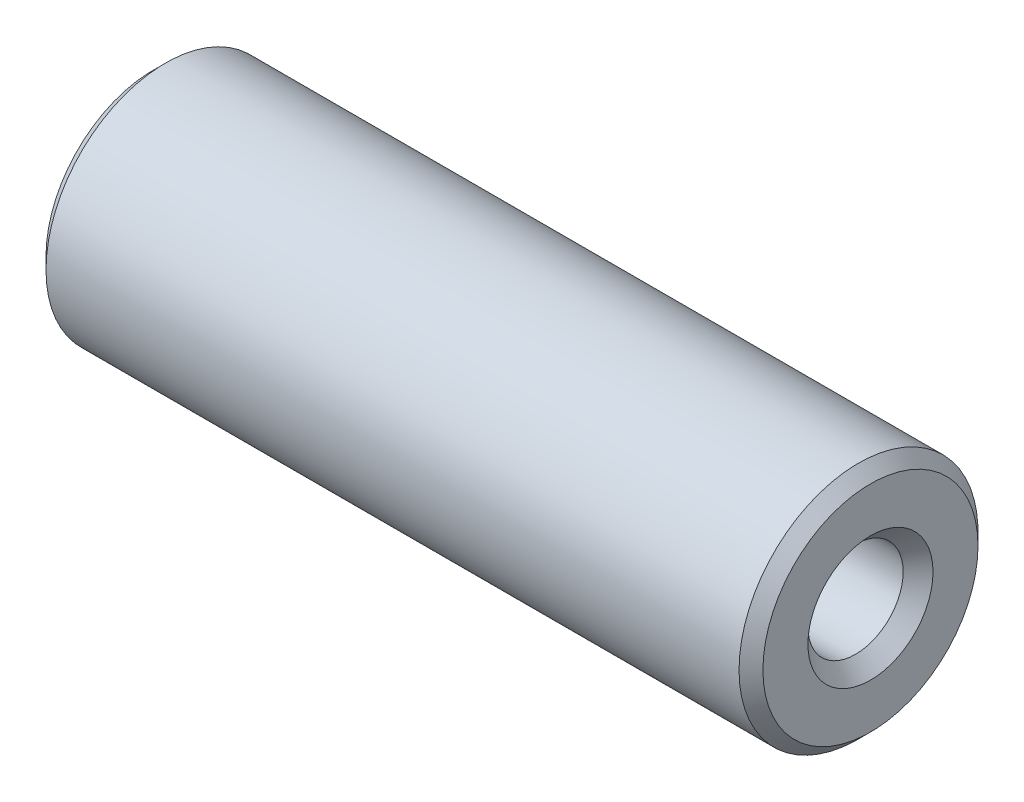
SolidWorks part; units mm, degrees
material "Ti-6Al-4VSolution treated and aged (SS)"
ref_plane "Front Plane" through (0, 0, 0) normal (0, 0, 1) x (1, 0, 0)
ref_plane "Top Plane" through (0, 0, 0) normal (0, 1, 0) x (1, 0, 0)
ref_plane "Right Plane" through (0, 0, 0) normal (1, 0, 0) x (0, 0, -1)
sketch "Sketch1" plane through (0, 0, 0) normal (1, 0, 0) x (0, 0, -1)
  circle A0 centre (0, 0) radius 10.1206
  circle A1 centre (0, 0) radius 25.4
  dimension "D1" = 50.8
  dimension "D2" = 20.2413
extrude "Boss-Extrude1" add sketch "Sketch1" along normal blind 152.4
chamfer "Chamfer1" distance 2.54 angle 45 2 edges at (0, 0, -25.4) (152.4, 0, -25.4)
chamfer "Chamfer2" distance 3.175 angle 45 2 edges at (0, 0, -10.1206) (152.4, 0, -10.1206)
ref_plane "Plane1" through (139.7, 0, 0) normal (1, 0, 0) x (0, 0, -1)
ref_plane "Plane2" through (12.7, 0, 0) normal (-1, 0, 0) x (0, 0, 1)
ref_plane "Plane3" through (76.2, 0, 0) normal (-1, 0, 0) x (0, 0, 1)
ref_plane "Plane4" through (44.45, 0, 0) normal (-1, 0, 0) x (0, 0, 1)
ref_plane "Plane5" through (107.95, 0, 0) normal (-1, 0, 0) x (0, 0, 1)
